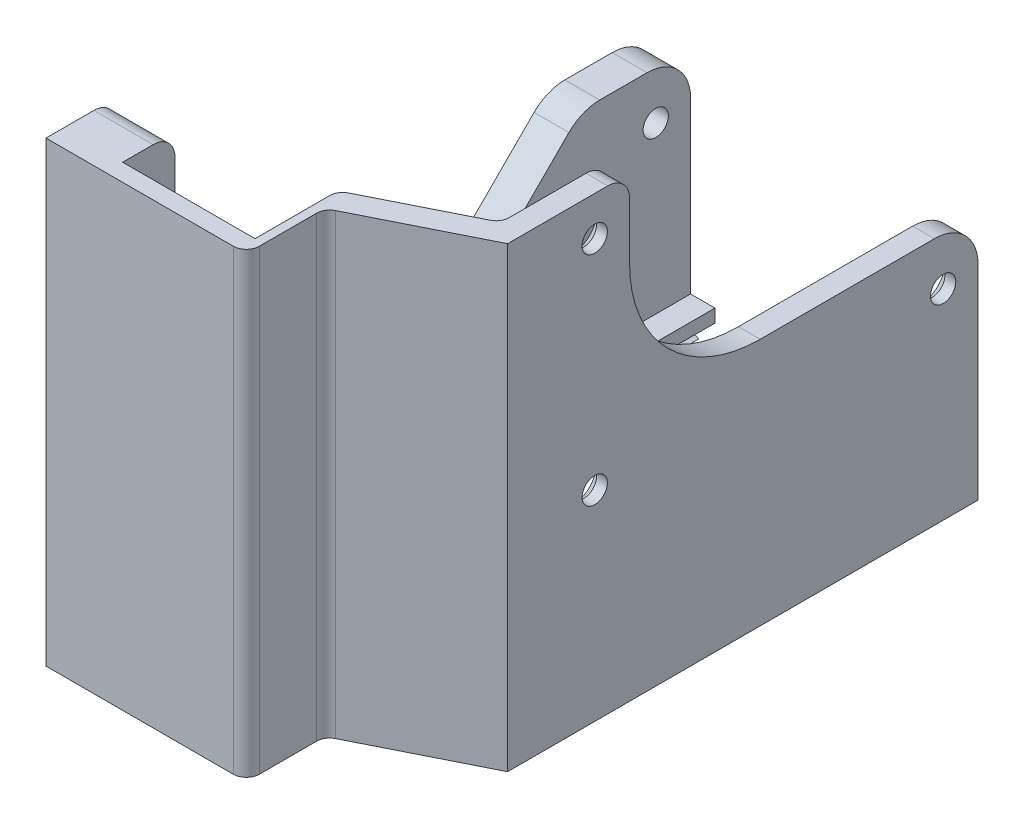
SolidWorks part; units mm, degrees
ref_plane "Спереди" through (0, 0, 0) normal (0, 0, 1) x (1, 0, 0)
ref_plane "Сверху" through (0, 0, 0) normal (0, 1, 0) x (1, 0, 0)
ref_plane "Справа" through (0, 0, 0) normal (1, 0, 0) x (0, 0, -1)
sketch "Эскиз2" plane through (0, 0, 0) normal (0, 1, 0) x (1, 0, 0)
  line L0 (0, -287.0595) -> (0, 0) construction
  line L1 (0, 0) -> (65.4832, 0) construction
  line L2 (52.3789, 0) -> (52.3789, -108)
  line L3 (52.3789, -108) -> (24.3789, -122)
  line L4 (24.3789, -122) -> (24.3789, -140)
  line L5 (24.3789, -140) -> (0, -140)
  line L8 (22.3789, 0) -> (22.3789, -136)
  line L9 (22.3789, -136) -> (0, -136)
  line L10 (0, -136) -> (-8.0211, -136)
  line L11 (-8.0211, -136) -> (-8.0211, 0)
  line L12 (-8.0211, 0) -> (-21.6211, 0)
  line L13 (-21.6211, 0) -> (-21.6211, -140)
  line L14 (-21.6211, -140) -> (0, -140)
  line L15 (22.3789, 0) -> (52.3789, 0)
  line L16 (-8.0211, -22.3266) -> (22.3789, -22.3266) construction
  line L17 (7.1789, -22.3266) -> (7.1789, 3.9751) construction
  dimension "D2" = 4
  dimension "D3" = 2
  dimension "D4" = 32
  dimension "D5" = 28
  dimension "D6" = 140
  dimension "D7" = 18
  dimension "D8" = 74
  dimension "D9" = 108
  dimension "D10" = 13.6
  dimension "D11" = 30.4
  dimension "D12" = 28.8
  dimension "D13" = 63.435
extrude "Бобышка-Вытянуть1" add sketch "Эскиз2" along normal blind 105
sketch "Эскиз4" plane through (0, 0, 0) normal (0, -1, 0) x (1, 0, 0)
  line L0 (-21.6211, 0) -> (52.3789, 0)
  line L1 (52.3789, 0) -> (52.3789, 108)
  line L2 (52.3789, 108) -> (24.3789, 122)
  line L3 (24.3789, 122) -> (24.3789, 140)
  line L4 (24.3789, 140) -> (-21.6211, 140)
  line L5 (-21.6211, 140) -> (-21.6211, 0)
sketch "Эскиз7" plane through (0, 0, 0) normal (0, -1, 0) x (1, 0, 0)
  line L0 (22.3789, 0) -> (22.3789, 136) construction
  line L1 (-8.0211, 136) -> (22.3789, 136)
  line L2 (-8.0211, 136) -> (-8.0211, 117)
  line L3 (-8.0211, 117) -> (22.3789, 117)
  line L4 (22.3789, 136) -> (22.3789, 117)
  dimension "D1" = 19
extrude "Бобышка-Вытянуть2" add sketch "Эскиз7" against normal blind 3 separate body
sketch "Эскиз8" plane through (0, 3, 0) normal (0, 1, 0) x (1, 0, 0)
  line L0 (-8.0211, -136) -> (-8.0211, -117) construction
  line L1 (22.3789, -136) -> (-8.0211, -136)
  line L2 (22.3789, -136) -> (22.3789, -124)
  line L3 (22.3789, -124) -> (-8.0211, -124)
  line L4 (-8.0211, -136) -> (-8.0211, -124)
  dimension "D1" = 12
extrude "Бобышка-Вытянуть3" add sketch "Эскиз8" along normal blind 38
fillet "Скругление1" radius 5 1 edges at (7.1789, 41, 124)
sketch "Эскиз3" plane through (0, 0, 0) normal (0, 0, -1) x (-1, 0, 0)
  line L0 (8.0211, -1.66) -> (19.3211, 3.4)
  line L1 (19.3211, 3.4) -> (19.3211, 5)
  line L2 (19.3211, 5) -> (8.0211, 5)
  line L3 (8.0211, 105) -> (8.0211, 0) construction
  line L4 (8.0211, 5) -> (8.0211, -1.66)
  line L5 (-7.1789, 0) -> (-7.1789, 26.9133) construction
  line L6 (-22.3789, 0) -> (8.0211, 0) construction
  line L7 (-33.6789, 5) -> (-22.3789, 5)
  line L8 (-33.6789, 3.4) -> (-33.6789, 5)
  line L9 (-22.3789, -1.66) -> (-33.6789, 3.4)
  line L10 (-22.3789, 5) -> (-22.3789, -1.66)
  line L11 (-24.3789, 0) -> (21.6211, 0) construction
  dimension "D1" = 6.66
  dimension "D2" = 1.6
  dimension "D3" = 5
  dimension "D4" = 53
  dimension "D5" = 15.2
  dimension "D6" = 15.2
  dimension "D7" = 11.3
extrude "Вырез-Вытянуть1" cut sketch "Эскиз3" against normal up to surface (117 mm away) up to face at (7.1789, 1.5, 117)
sketch "Эскиз9" plane through (0, 105, 0) normal (0, 1, 0) x (1, 0, 0)
  line L0 (-21.6211, 0) -> (-21.6211, -96)
  line L1 (-21.6211, 0) -> (52.3789, 0) construction
  line L2 (-21.6211, -96) -> (22.3789, -96)
  line L3 (22.3789, 0) -> (22.3789, -136) construction
  line L4 (22.3789, -124) -> (22.3789, -129) construction
  line L5 (22.3789, -96) -> (22.3789, -117)
  line L6 (-8.0211, -117) -> (22.3789, -117) construction
  line L7 (22.3789, -117) -> (47.3789, -104.5)
  line L8 (47.3789, -104.5) -> (47.3789, 0)
  line L9 (47.3789, 0) -> (-21.6211, 0)
  line L10 (22.3789, -136) -> (-8.0211, -136) construction
  line L13 (52.3789, 0) -> (52.3789, -108) construction
  line L14 (52.3789, -108) -> (24.3789, -122) construction
  dimension "D1" = 40
  dimension "D2" = 5.3666
  dimension "D3" = 5
extrude "Вырез-Вытянуть2" cut sketch "Эскиз9" against normal offset from surface (97 mm away) 3 up to face at (28.0289, 5, 58.5)
sketch "Эскиз11" plane through (-21.6211, 0, 0) normal (-1, 0, 0) x (0, 0, 1)
  line L0 (103.6, 88.4738) -> (103.6, 19.9227) construction
  line L1 (122, 0) -> (140, 0) construction
  line L2 (140, 105) -> (140, 0) construction
  circle A0 centre (103.6, 41.2) radius 5
  dimension "D2" = 10
  dimension "D3" = 41.2
  dimension "D4" = 36.4
extrude "Вырез-Вытянуть4" cut sketch "Эскиз11" against normal blind 6.8 and the other way through all
fillet "Скругление3" radius 3 4 edges at (47.3789, 56.5, 104.5) (24.3789, 52.5, 122) (24.3789, 52.5, 140) (22.3789, 56.5, 117)
sketch "Эскиз12" plane through (-21.6211, 0, 0) normal (-1, 0, 0) x (0, 0, 1)
  circle A0 centre (103.6, 41.2) radius 2.6
  dimension "D1" = 5.2
extrude "Вырез-Вытянуть5" cut sketch "Эскиз12" against normal blind 20
chamfer "Фаска1" distance 3 angle 45 1 edges at (-14.8211, 41.2, 106.2)
sketch "Эскиз13" plane through (-21.6211, 0, 0) normal (-1, 0, 0) x (0, 0, 1)
  line L0 (140, 105) -> (140, 0) construction
  line L1 (33.0864, 46) -> (88, 46) construction
  line L2 (88, 46) -> (88, 141.3627) construction
  line L3 (0, 0) -> (108, 0) construction
  circle A0 centre (88, 46) radius 2.9
  circle A1 centre (8, 46) radius 2.9
  circle A3 centre (88, 96) radius 2.9
  dimension "D1" = 5.8
  dimension "D2" = 50
  dimension "D3" = 80
  dimension "D4" = 52
  dimension "D5" = 46
  dimension "D6" = 20
extrude "Вырез-Вытянуть6" cut sketch "Эскиз13" against normal through all
chamfer "Фаска3" distance 2.5 angle 45 3 edges at (47.3789, 46, 5.1) (47.3789, 46, 85.1) (47.3789, 96, 85.1)
sketch "Эскиз16" plane through (-21.6211, 0, 0) normal (-1, 0, 0) x (0, 0, 1)
  line L0 (80, 105) -> (80, 57)
  line L1 (96, 105) -> (140, 105) construction
  line L2 (80, 57) -> (0, 57)
  line L3 (0, 8) -> (0, 0) construction
  line L4 (0, 57) -> (0, 105)
  line L5 (0, 105) -> (80, 105)
  line L6 (140, 105) -> (140, 0) construction
  dimension "D1" = 60
  dimension "D2" = 48
extrude "Вырез-Вытянуть9" cut sketch "Эскиз16" against normal through all
fillet "Скругление4" radius 30 1 edges at (49.8789, 57, 80)
sketch "Эскиз17" plane through (-21.6211, 0, 0) normal (-1, 0, 0) x (0, 0, 1)
  line L0 (96, 105) -> (140, 105) construction
  line L1 (124, 105) -> (96, 105)
  line L2 (124, 105) -> (124, 53)
  line L3 (124, 53) -> (96, 53)
  line L4 (96, 105) -> (96, 53)
  line L5 (96, 8) -> (96, 105) construction
  line L6 (140, 105) -> (140, 0) construction
  dimension "D1" = 16
  dimension "D2" = 52
extrude "Вырез-Вытянуть10" cut sketch "Эскиз17" against normal blind 20
fillet "Скругление5" radius 8 2 edges at (-14.8211, 53, 124) (-14.8211, 53, 96)
sketch "Эскиз18" plane through (0, 8, 0) normal (0, 1, 0) x (1, 0, 0)
  line L0 (-21.6211, -140) -> (-21.6211, 0) construction
  line L1 (-13.6211, -24) -> (-21.6211, -24)
  line L2 (-13.6211, -24) -> (-13.6211, 0)
  line L3 (-13.6211, 0) -> (-21.6211, 0)
  line L4 (-21.6211, -24) -> (-21.6211, 0)
  line L5 (24.3789, -140) -> (-21.6211, -140) construction
  dimension "D1" = 8
  dimension "D3" = 116
extrude "Бобышка-Вытянуть4" add sketch "Эскиз18" along normal up to surface (49 mm away) up to face at (49.8789, 57, 25)
chamfer "Фаска4" distance 50 angle 45 1 edges at (-17.6211, 8, 24)
fillet "Скругление6" radius 10 2 edges at (49.8789, 57, 0) (-17.6211, 57, 0)
sketch "Эскиз19" plane through (52.3789, 0, 0) normal (1, 0, 0) x (0, 0, -1)
  circle A0 centre (-8, 46) radius 2.9
extrude "Вырез-Вытянуть11" cut sketch "Эскиз19" against normal through all
chamfer "Фаска5" distance 2.6 angle 45 1 edges at (-21.6211, 46, 5.1)
sketch "Эскиз21" plane through (-21.6211, 0, 0) normal (-1, 0, 0) x (0, 0, 1)
  line L0 (130, 108.683) -> (130, -7.686) construction
  line L1 (140, 105) -> (140, 0) construction
  line L2 (122, 0) -> (140, 0) construction
  circle A0 centre (130, 30) radius 2.3
  circle A1 centre (130, 90) radius 2.3
  dimension "D2" = 4.6
  dimension "D3" = 60
  dimension "D1" = 10
  dimension "D4" = 30
extrude "Вырез-Вытянуть13" cut sketch "Эскиз21" against normal blind 15
fillet "Скругление7" radius 5 2 edges at (-14.8211, 105, 124) (49.8789, 105, 80)
chamfer "Фаска6" distance 0.8 angle 45 3 edges at (-21.6211, 41.2, 98.6) (-21.6211, 30, 132.3) (-21.6211, 90, 132.3)
sketch "Эскиз22" plane through (0, 8, 0) normal (0, 1, 0) x (1, 0, 0)
  line L0 (-13.6211, -25) -> (-13.6211, -74) construction
  line L1 (-21.6211, -96) -> (-13.6211, -96)
  line L2 (-21.6211, -96) -> (-21.6211, -47.3162)
  line L3 (-21.6211, -47.3162) -> (-13.6211, -47.3162)
  line L4 (-13.6211, -96) -> (-13.6211, -47.3162)
  line L5 (-13.6211, -74) -> (-13.6211, 0) construction
extrude "Бобышка-Вытянуть5" add sketch "Эскиз22" along normal blind 10
fillet "Скругление8" radius 10 1 edges at (-17.6211, 57, 25)
